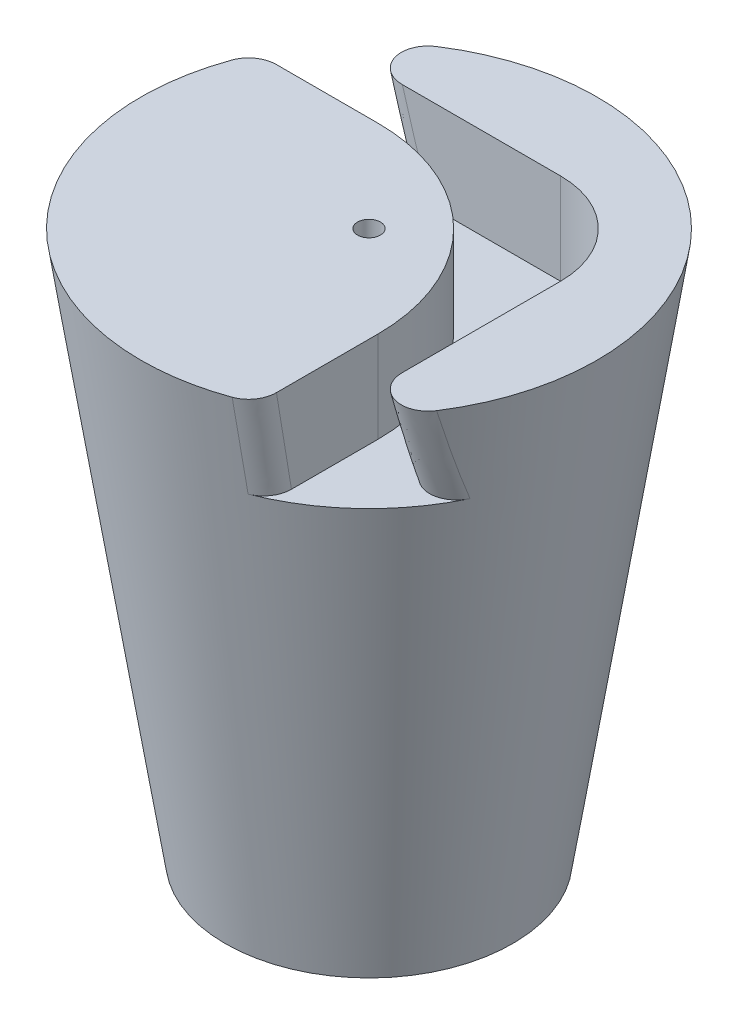
SolidWorks part; units mm, degrees
ref_plane "Front Plane" through (0, 0, 0) normal (0, 0, 1) x (1, 0, 0)
ref_plane "Top Plane" through (0, 0, 0) normal (0, 1, 0) x (1, 0, 0)
ref_plane "Right Plane" through (0, 0, 0) normal (1, 0, 0) x (0, 0, -1)
sketch "Sketch2" plane through (0, 0, 0) normal (0, 1, 0) x (1, 0, 0)
  line L1 (-25, -25) -> (25, -25)
  line L2 (-25, -25) -> (-25, 25)
  line L3 (-25, 25) -> (25, 25)
  line L4 (25, -25) -> (25, 25)
  line L5 (0, 25) -> (0, -25) construction
  line L6 (-25, 0) -> (25, 0) construction
  point P0 (0, 0)
extrude "Boss-Extrude1" add sketch "Sketch2" along normal blind 60
sketch "Sketch3" plane through (0, 60, 0) normal (0, 1, 0) x (1, 0, 0)
  line L0 (-25, 13) -> (13, 13) construction
  line L1 (-25, 25) -> (-25, -25) construction
  line L2 (13, 13) -> (13, -25) construction
  line L3 (-25, -25) -> (25, -25) construction
  line L4 (25, -25) -> (25, 25) construction
  line L5 (25, 25) -> (-25, 25) construction
  line L6 (-25, 10.5) -> (10.5, 10.5)
  line L7 (10.5, 10.5) -> (10.5, -25)
  line L8 (-25, 15.5) -> (15.5, 15.5)
  line L9 (15.5, 15.5) -> (15.5, -25)
  line L10 (-25, 15.5) -> (-25, 10.5)
  line L11 (10.5, -25) -> (15.5, -25)
  dimension "D3" = 2.5
  dimension "D4" = 2.5
extrude "Cut-Extrude1" cut sketch "Sketch3" against normal blind 10
fillet "Fillet1" radius 20 1 edges at (10.5, 55, -10.5)
sketch "Sketch4" plane through (0, 60, 0) normal (0, 1, 0) x (1, 0, 0)
  line L0 (-25, -25) -> (25, -25) construction
  circle A0 centre (0, 0) radius 25
extrude "Cut-Extrude2" cut sketch "Sketch4" against normal through all draft 8.75 flip side to cut draft outward yes
fillet "Fillet2" radius 10 1 edges at (15.5, 55, -15.5)
sketch "Sketch5" plane through (0, 0, 0) normal (0, -1, 0) x (1, 0, 0)
  circle A0 centre (0, 0) radius 7
  dimension "D1" = 14
extrude "Cut-Extrude3" cut sketch "Sketch5" against normal blind 2.2
fillet "Fillet3" radius 3 4 edges
hole_wizard "M3x0.5 Tapped Hole1" positions "Sketch6" profile "Sketch7" tap size "M3x0.5" standard "ANSI Metric" end condition through all
sketch "Sketch6" plane through (0, 2.2, 0) normal (0, -1, 0) x (-1, 0, 0)
  point P0 (0, 0)
sketch "Sketch7" plane through (0, 2.2, 0) normal (1, 0, 0) x (0, 0, -1)
  line L0 (0, 0) -> (0, 57.8)
  line L1 (0, 57.8) -> (1.25, 57.8)
  line L2 (1.25, 57.8) -> (1.25, 0)
  line L5 (1.25, 0) -> (0, 0)
  line L11 (0, -6.35) -> (0, 107.95) construction
  dimension "Thru Tap Drill Dia." = 2.5
  dimension "Thru Tap Drill Depth" = 57.8
cosmetic thread "Hole Thread1" parameters "D2"=3
